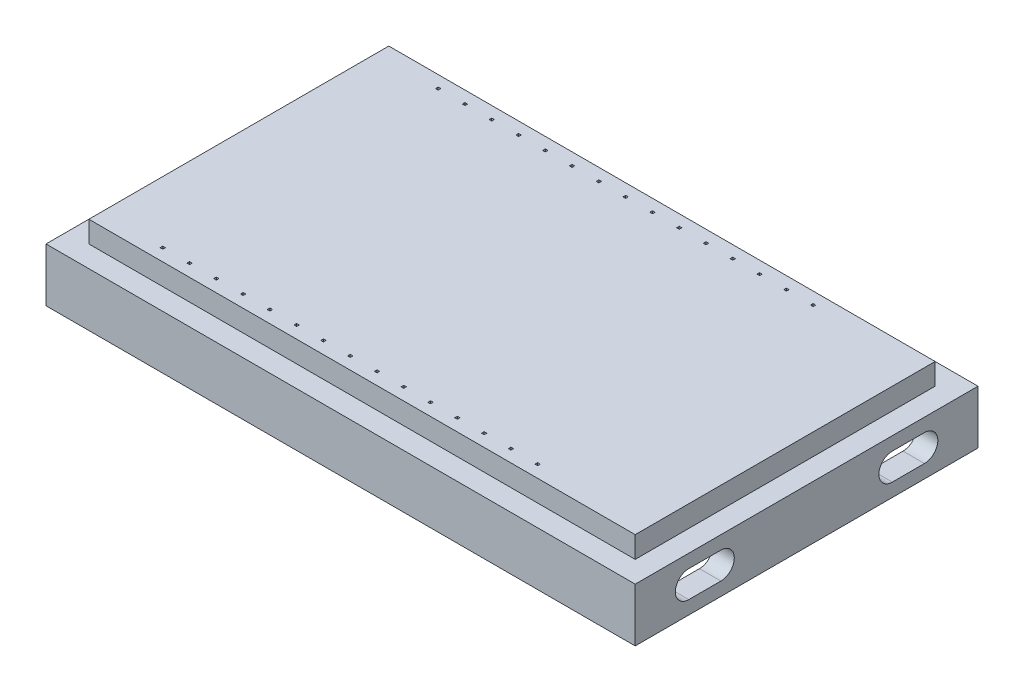
SolidWorks part; units mm, degrees
ref_plane "Alzado" through (0, 0, 0) normal (0, 0, 1) x (1, 0, 0)
ref_plane "Planta" through (0, 0, 0) normal (0, 1, 0) x (1, 0, 0)
ref_plane "Vista lateral" through (0, 0, 0) normal (1, 0, 0) x (0, 0, -1)
sketch "Croquis1" plane through (0, 0, 0) normal (0, 1, 0) x (1, 0, 0)
  line L0 (16.5, 12.85) -> (-21, 12.85) construction
  line L1 (25.5, -14) -> (-25.5, -14)
  line L2 (25.5, -14) -> (25.5, 14)
  line L3 (25.5, 14) -> (-25.5, 14)
  line L4 (-25.5, -14) -> (-25.5, 14)
  line L5 (25.5, -14) -> (-25.5, 14) construction
  line L6 (25.5, 14) -> (-25.5, -14) construction
  line L7 (-27.5, -16) -> (27.5, -16)
  line L8 (-27.5, -16) -> (-27.5, 16)
  line L9 (-27.5, 16) -> (27.5, 16)
  line L10 (27.5, -16) -> (27.5, 16)
  line L11 (-27.5, -16) -> (27.5, 16) construction
  line L12 (-27.5, 16) -> (27.5, -16) construction
  line L13 (-21, 14) -> (16.5, 14)
  line L14 (-21, 14) -> (-21, 11.7)
  line L15 (-21, 11.7) -> (16.5, 11.7)
  line L16 (16.5, 14) -> (16.5, 11.7)
  line L17 (-21, -11.7) -> (16.5, -11.7)
  line L18 (-21, -11.7) -> (-21, -14)
  line L19 (-21, -14) -> (16.5, -14)
  line L20 (16.5, -11.7) -> (16.5, -14)
  line L21 (-21, -12.85) -> (16.5, -12.85)
  line L22 (12.625, -12.975) -> (12.625, -12.725)
  line L23 (12.6211, 12.7384) -> (12.6211, 12.9884)
  line L24 (15.1211, 12.7384) -> (15.3711, 12.7384)
  line L25 (15.1211, 12.7384) -> (15.1211, 12.9884)
  line L26 (15.1211, 12.9884) -> (15.3711, 12.9884)
  line L27 (15.3711, 12.7384) -> (15.3711, 12.9884)
  line L28 (15.1211, 12.7384) -> (15.3711, 12.9884) construction
  line L29 (15.1211, 12.9884) -> (15.3711, 12.7384) construction
  line L30 (12.6211, 12.7384) -> (12.8711, 12.7384)
  line L31 (12.8711, 12.7384) -> (12.8711, 12.9884)
  line L32 (12.6211, 12.9884) -> (12.8711, 12.9884)
  line L33 (10.1211, 12.7384) -> (10.1211, 12.9884)
  line L34 (10.1211, 12.7384) -> (10.3711, 12.7384)
  line L35 (10.3711, 12.7384) -> (10.3711, 12.9884)
  line L36 (10.1211, 12.9884) -> (10.3711, 12.9884)
  line L37 (7.6211, 12.7384) -> (7.6211, 12.9884)
  line L38 (7.6211, 12.7384) -> (7.8711, 12.7384)
  line L39 (7.8711, 12.7384) -> (7.8711, 12.9884)
  line L40 (7.6211, 12.9884) -> (7.8711, 12.9884)
  line L41 (5.1211, 12.7384) -> (5.1211, 12.9884)
  line L42 (5.1211, 12.7384) -> (5.3711, 12.7384)
  line L43 (5.3711, 12.7384) -> (5.3711, 12.9884)
  line L44 (5.1211, 12.9884) -> (5.3711, 12.9884)
  line L45 (2.6211, 12.7384) -> (2.6211, 12.9884)
  line L46 (2.6211, 12.7384) -> (2.8711, 12.7384)
  line L47 (2.8711, 12.7384) -> (2.8711, 12.9884)
  line L48 (2.6211, 12.9884) -> (2.8711, 12.9884)
  line L49 (0.1211, 12.7384) -> (0.1211, 12.9884)
  line L50 (0.1211, 12.7384) -> (0.3711, 12.7384)
  line L51 (0.3711, 12.7384) -> (0.3711, 12.9884)
  line L52 (0.1211, 12.9884) -> (0.3711, 12.9884)
  line L53 (-2.3789, 12.7384) -> (-2.3789, 12.9884)
  line L54 (-2.3789, 12.7384) -> (-2.1289, 12.7384)
  line L55 (-2.1289, 12.7384) -> (-2.1289, 12.9884)
  line L56 (-2.3789, 12.9884) -> (-2.1289, 12.9884)
  line L57 (-4.8789, 12.7384) -> (-4.8789, 12.9884)
  line L58 (-4.8789, 12.7384) -> (-4.6289, 12.7384)
  line L59 (-4.6289, 12.7384) -> (-4.6289, 12.9884)
  line L60 (-4.8789, 12.9884) -> (-4.6289, 12.9884)
  line L61 (-7.3789, 12.7384) -> (-7.3789, 12.9884)
  line L62 (-7.3789, 12.7384) -> (-7.1289, 12.7384)
  line L63 (-7.1289, 12.7384) -> (-7.1289, 12.9884)
  line L64 (-7.3789, 12.9884) -> (-7.1289, 12.9884)
  line L65 (-9.8789, 12.7384) -> (-9.8789, 12.9884)
  line L66 (-9.8789, 12.7384) -> (-9.6289, 12.7384)
  line L67 (-9.6289, 12.7384) -> (-9.6289, 12.9884)
  line L68 (-9.8789, 12.9884) -> (-9.6289, 12.9884)
  line L69 (-12.3789, 12.7384) -> (-12.3789, 12.9884)
  line L70 (-12.3789, 12.7384) -> (-12.1289, 12.7384)
  line L71 (-12.1289, 12.7384) -> (-12.1289, 12.9884)
  line L72 (-12.3789, 12.9884) -> (-12.1289, 12.9884)
  line L73 (-14.8789, 12.7384) -> (-14.8789, 12.9884)
  line L74 (-14.8789, 12.7384) -> (-14.6289, 12.7384)
  line L75 (-14.6289, 12.7384) -> (-14.6289, 12.9884)
  line L76 (-14.8789, 12.9884) -> (-14.6289, 12.9884)
  line L77 (-17.3789, 12.7384) -> (-17.3789, 12.9884)
  line L78 (-17.3789, 12.7384) -> (-17.1289, 12.7384)
  line L79 (-17.1289, 12.7384) -> (-17.1289, 12.9884)
  line L80 (-17.3789, 12.9884) -> (-17.1289, 12.9884)
  line L81 (-19.8789, 12.7384) -> (-19.8789, 12.9884)
  line L82 (-19.8789, 12.7384) -> (-19.6289, 12.7384)
  line L83 (-19.6289, 12.7384) -> (-19.6289, 12.9884)
  line L84 (-19.8789, 12.9884) -> (-19.6289, 12.9884)
  line L85 (15.125, -12.975) -> (15.375, -12.975)
  line L86 (15.125, -12.975) -> (15.125, -12.725)
  line L87 (15.125, -12.725) -> (15.375, -12.725)
  line L88 (15.375, -12.975) -> (15.375, -12.725)
  line L89 (15.125, -12.975) -> (15.375, -12.725) construction
  line L90 (15.125, -12.725) -> (15.375, -12.975) construction
  line L91 (12.625, -12.975) -> (12.875, -12.975)
  line L92 (12.875, -12.975) -> (12.875, -12.725)
  line L93 (12.625, -12.725) -> (12.875, -12.725)
  line L94 (10.125, -12.975) -> (10.125, -12.725)
  line L95 (10.125, -12.975) -> (10.375, -12.975)
  line L96 (10.375, -12.975) -> (10.375, -12.725)
  line L97 (10.125, -12.725) -> (10.375, -12.725)
  line L98 (7.625, -12.975) -> (7.625, -12.725)
  line L99 (7.625, -12.975) -> (7.875, -12.975)
  line L100 (7.875, -12.975) -> (7.875, -12.725)
  line L101 (7.625, -12.725) -> (7.875, -12.725)
  line L102 (5.125, -12.975) -> (5.125, -12.725)
  line L103 (5.125, -12.975) -> (5.375, -12.975)
  line L104 (5.375, -12.975) -> (5.375, -12.725)
  line L105 (5.125, -12.725) -> (5.375, -12.725)
  line L106 (2.625, -12.975) -> (2.625, -12.725)
  line L107 (2.625, -12.975) -> (2.875, -12.975)
  line L108 (2.875, -12.975) -> (2.875, -12.725)
  line L109 (2.625, -12.725) -> (2.875, -12.725)
  line L110 (0.125, -12.975) -> (0.125, -12.725)
  line L111 (0.125, -12.975) -> (0.375, -12.975)
  line L112 (0.375, -12.975) -> (0.375, -12.725)
  line L113 (0.125, -12.725) -> (0.375, -12.725)
  line L114 (-2.375, -12.975) -> (-2.375, -12.725)
  line L115 (-2.375, -12.975) -> (-2.125, -12.975)
  line L116 (-2.125, -12.975) -> (-2.125, -12.725)
  line L117 (-2.375, -12.725) -> (-2.125, -12.725)
  line L118 (-4.875, -12.975) -> (-4.875, -12.725)
  line L119 (-4.875, -12.975) -> (-4.625, -12.975)
  line L120 (-4.625, -12.975) -> (-4.625, -12.725)
  line L121 (-4.875, -12.725) -> (-4.625, -12.725)
  line L122 (-7.375, -12.975) -> (-7.375, -12.725)
  line L123 (-7.375, -12.975) -> (-7.125, -12.975)
  line L124 (-7.125, -12.975) -> (-7.125, -12.725)
  line L125 (-7.375, -12.725) -> (-7.125, -12.725)
  line L126 (-9.875, -12.975) -> (-9.875, -12.725)
  line L127 (-9.875, -12.975) -> (-9.625, -12.975)
  line L128 (-9.625, -12.975) -> (-9.625, -12.725)
  line L129 (-9.875, -12.725) -> (-9.625, -12.725)
  line L130 (-12.375, -12.975) -> (-12.375, -12.725)
  line L131 (-12.375, -12.975) -> (-12.125, -12.975)
  line L132 (-12.125, -12.975) -> (-12.125, -12.725)
  line L133 (-12.375, -12.725) -> (-12.125, -12.725)
  line L134 (-14.875, -12.975) -> (-14.875, -12.725)
  line L135 (-14.875, -12.975) -> (-14.625, -12.975)
  line L136 (-14.625, -12.975) -> (-14.625, -12.725)
  line L137 (-14.875, -12.725) -> (-14.625, -12.725)
  line L138 (-17.375, -12.975) -> (-17.375, -12.725)
  line L139 (-17.375, -12.975) -> (-17.125, -12.975)
  line L140 (-17.125, -12.975) -> (-17.125, -12.725)
  line L141 (-17.375, -12.725) -> (-17.125, -12.725)
  line L142 (-19.875, -12.975) -> (-19.875, -12.725)
  line L143 (-19.875, -12.975) -> (-19.625, -12.975)
  line L144 (-19.625, -12.975) -> (-19.625, -12.725)
  line L145 (-19.875, -12.725) -> (-19.625, -12.725)
  point P0 (0, 0)
  point P6 (0, 0)
  point P23 (15.25, -12.85)
  point P25 (15.2461, 12.8634)
  dimension "D1" = 51
  dimension "D2" = 28
  dimension "D3" = 55
  dimension "D4" = 32
  dimension "D5" = 37.5
  dimension "D6" = 9
  dimension "D7" = 2.3
  dimension "D8" = 2.3
  dimension "D9" = 0.25
  dimension "D10" = 0.25
  dimension "D11" = 1.25
  dimension "D12" = 0.25
  dimension "D13" = 0.25
  dimension "D14" = 15
extrude "Saliente-Extruir1" add sketch "Croquis1" along normal blind 2 contours L17 L20 L1 L2 L3 L16 L15 L14 L4 L18 | L142 L145 L144 L21 L138 L141 L140 L134 L137 L136 L130 L133 L132 L126 L129 L128 L122 L125 L124 L118 L121 L120 L114 L117 L116 L110 L113 L112 L106 L109 L108 L102 L105 L104 L98 L101 L100 L94 L97 L96 | L144 L143 L142 L21 L18 L1 L20 L88 L85 L86 L92 L91 L22 L96 L95 L94 L100 L99 L98 L104 L103 L102 L108 L107 L106 L112 L111 L110 L116 L115 L114 L120 L119 L118 L124 L123 L122 L128 L127 L126 | L16 L3 L14 L15 L27 L24 L25 L26 L23 L32 L31 L30 L33 L36 L35 L34 L37 L40 L39 L38 L41 L44 L43 L42 L45 L48 L47 L46 L49 L52 L51 L50 L53 L56 L55 L54 L57 L60 L59 L58 L61 region at (0.3091, 0, 0) region at (-2.25, 0, 13.4306) region at (-2.25, 0, 12.2694) region at (16.1243, 0, -12.85)
extrude "Saliente-Extruir2" add sketch "Croquis1<3>" against normal blind 5 separate body contours L7 L10 L9 L8 L1 L4 L3 L2 region at (-26.8637, 0, 0)
sketch "Croquis1<3>" plane through (0, 0, 0) normal (0, 1, 0) x (1, 0, 0) same geometry as "Croquis1"
sketch "Croquis2" plane through (-27.5, 0, 0) normal (-1, 0, 0) x (0, 0, 1)
  line L0 (8, -2.5) -> (11, -2.5) construction
  line L1 (8, -1.25) -> (11, -1.25)
  line L2 (8, -3.75) -> (11, -3.75)
  line L3 (16, -5) -> (16, 0) construction
  line L4 (16, 0) -> (-16, 0) construction
  arc A0 (8, -1.25) -> (8, -3.75) centre (8, -2.5) ccw
  arc A1 (11, -3.75) -> (11, -1.25) centre (11, -2.5) ccw
  point P2 (9.5, -2.5)
  dimension "D1" = 5
  dimension "D2" = 3
  dimension "D3" = 2.5
  dimension "D4" = 2.5
extrude "Cortar-Extruir1" cut sketch "Croquis2" against normal blind 70 contours L2 A1 L1 A0
sketch "Croquis3" plane through (27.5, 0, 0) normal (1, 0, 0) x (0, 0, -1)
  line L0 (8, -2.5) -> (11, -2.5) construction
  line L1 (8, -1.25) -> (11, -1.25)
  line L2 (8, -3.75) -> (11, -3.75)
  line L3 (16, -5) -> (16, 0) construction
  line L4 (-16, 0) -> (16, 0) construction
  arc A0 (8, -1.25) -> (8, -3.75) centre (8, -2.5) ccw
  arc A1 (11, -3.75) -> (11, -1.25) centre (11, -2.5) ccw
  point P2 (9.5, -2.5)
  dimension "D1" = 5
  dimension "D2" = 2.5
  dimension "D3" = 3
  dimension "D4" = 2.5
extrude "Cortar-Extruir2" cut sketch "Croquis3" against normal blind 5 contours L2 A1 L1 A0
